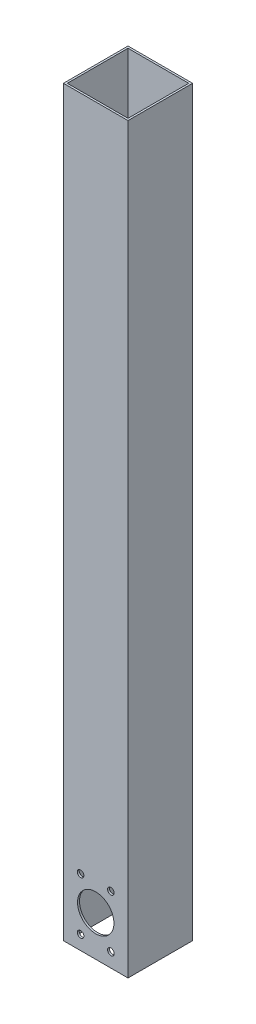
SolidWorks part; units mm, degrees
material "6061 Alloy"
ref_plane "Front Plane" through (0, 0, 0) normal (0, 0, 1) x (1, 0, 0)
ref_plane "Top Plane" through (0, 0, 0) normal (0, 1, 0) x (1, 0, 0)
ref_plane "Right Plane" through (0, 0, 0) normal (1, 0, 0) x (0, 0, -1)
sketch "Sketch1" plane through (0, 0, 0) normal (0, 1, 0) x (1, 0, 0)
  line L1 (25.4, 25.4) -> (-25.4, 25.4)
  line L2 (25.4, 25.4) -> (25.4, -25.4)
  line L3 (25.4, -25.4) -> (-25.4, -25.4)
  line L4 (-25.4, 25.4) -> (-25.4, -25.4)
  line L5 (25.4, 25.4) -> (-25.4, -25.4) construction
  line L6 (25.4, -25.4) -> (-25.4, 25.4) construction
  point P0 (0, 0)
  dimension "D1" = 50.8
extrude "Extrude-Thin1" add sketch "Sketch1" along normal blind 584.2 thin thin type one direction reverse wall 1.524
sketch "Sketch2" plane through (0, 0, 0) normal (0, 0, 1) x (1, 0, 0)
  line L0 (-36.2563, 49.2125) -> (38.5702, 49.2125) construction
  line L1 (-25.4, 0) -> (25.4, 0) construction
  line L2 (-25.4, 31.75) -> (25.4, 31.75) construction
  line L6 (25.4, 584.2) -> (25.4, 0) construction
  line L7 (-25.4, 584.2) -> (-25.4, 0) construction
  line L8 (-11.9126, 11.1168) -> (11.9126, 11.1168) construction
  line L9 (-11.9126, 52.3832) -> (11.9126, 52.3832) construction
  circle A0 centre (0, 31.75) radius 14.3002
  circle A1 centre (0, 31.75) radius 23.8252 construction
  circle A2 centre (-11.9126, 11.1168) radius 2.5908
  circle A3 centre (11.9126, 11.1168) radius 2.5908
  circle A4 centre (11.9126, 52.3832) radius 2.5908
  circle A5 centre (-11.9126, 52.3832) radius 2.5908
  point P11 (0, 31.75)
  dimension "D1" = 28.6004
  dimension "D3" = 17.4625
  dimension "D4" = 47.6504
  dimension "D6" = 5.1816
  dimension "D2" = 31.75
  dimension "D5" = 23.8252
extrude "Cut-Extrude1" cut sketch "Sketch2" along normal through all both and the other way through all
